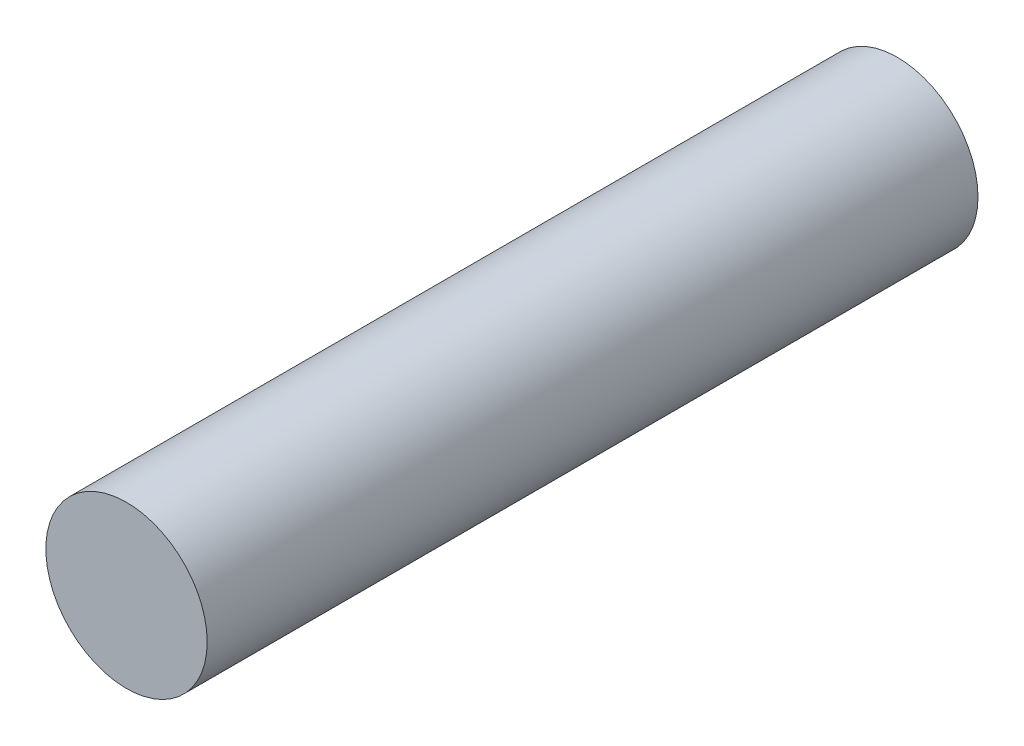
SolidWorks part; units mm, degrees
ref_plane "Front Plane" through (0, 0, 0) normal (0, 0, 1) x (1, 0, 0)
ref_plane "Top Plane" through (0, 0, 0) normal (0, 1, 0) x (1, 0, 0)
ref_plane "Right Plane" through (0, 0, 0) normal (1, 0, 0) x (0, 0, -1)
sketch "Sketch1" plane through (0, 0, 0) normal (0, 0, 1) x (1, 0, 0)
  circle A0 centre (0, 0) radius 2.25
  dimension "D1" = 4.5
extrude "Boss-Extrude1" add sketch "Sketch1" along normal blind 8 and the other way blind 13.5
sketch "Sketch2" plane through (0, 0, 0) normal (0, 0, 1) x (1, 0, 0)
  circle A0 centre (0, 0) radius 2.5 construction
  dimension "D1" = 5
